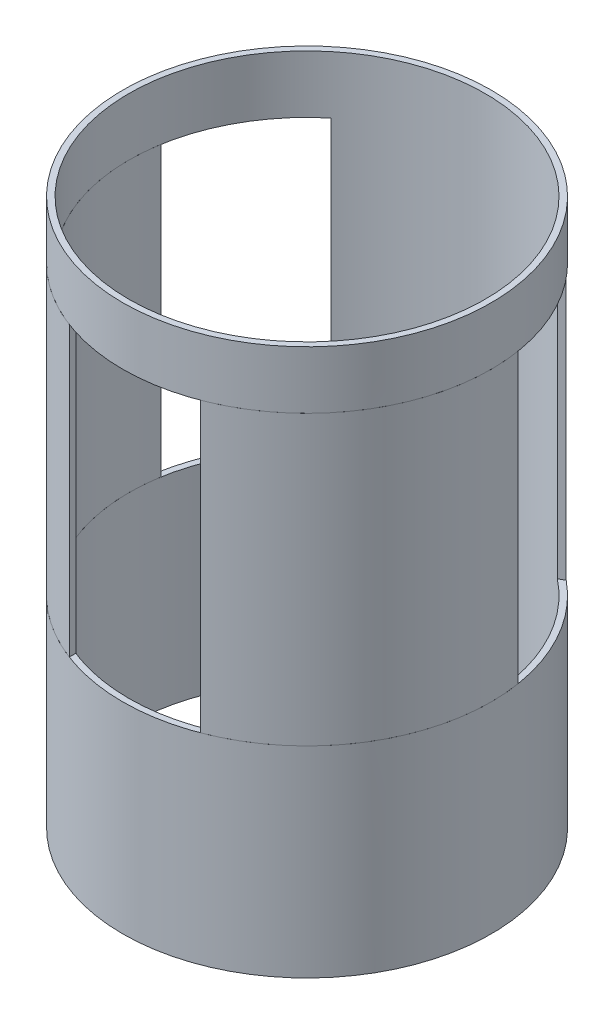
SolidWorks part; units mm, degrees
material "Carbon Fiber"
ref_plane "Front Plane" through (0, 0, 0) normal (0, 0, 1) x (1, 0, 0)
ref_plane "Top Plane" through (0, 0, 0) normal (0, 1, 0) x (1, 0, 0)
ref_plane "Right Plane" through (0, 0, 0) normal (1, 0, 0) x (0, 0, -1)
sketch "Sketch1" plane through (0, 0, 0) normal (0, 1, 0) x (1, 0, 0)
  line L0 (0, 0) -> (0, -68.75) construction
  line L1 (68.75, 0) -> (-68.75, 0) construction
  line L2 (-56.7965, 32.7915) -> (-44.5606, 53.9848)
  line L3 (0, 0) -> (59.5392, 34.375) construction
  line L4 (0, 0) -> (-59.5392, 34.375) construction
  line L5 (-44.5606, 53.9848) -> (-69.0325, 11.5982)
  line L6 (-54.2965, 37.1216) -> (-59.2965, 28.4614)
  line L7 (-59.2965, 28.4614) -> (-42.7188, 18.8902)
  line L8 (0, -65.583) -> (-24.4719, -65.583)
  line L9 (-24.4719, -65.583) -> (24.4719, -65.583)
  line L10 (-42.7188, 18.8902) -> (-37.7188, 27.5505)
  line L11 (-59.2965, 28.4614) -> (-61.8816, 29.9538)
  line L12 (-54.2965, 37.1216) -> (-37.7188, 27.5505)
  line L13 (-51.7965, 41.4517) -> (-55, 43.3013)
  line L14 (-61.7965, 24.1312) -> (-65, 25.9808)
  line L15 (-51.7965, 41.4517) -> (-30.8887, 29.3806) construction
  line L16 (-40.8887, 12.0601) -> (-30.8887, 29.3806) construction
  line L17 (-61.7965, 24.1312) -> (-40.8887, 12.0601) construction
  line L18 (56.7965, 32.7915) -> (69.0325, 11.5982)
  line L19 (69.0325, 11.5982) -> (44.5606, 53.9848)
  line L20 (59.2965, 28.4614) -> (54.2965, 37.1216)
  line L21 (54.2965, 37.1216) -> (37.7188, 27.5505)
  line L22 (37.7188, 27.5505) -> (42.7188, 18.8902)
  line L23 (54.2965, 37.1216) -> (56.8816, 38.6141)
  line L24 (59.2965, 28.4614) -> (42.7188, 18.8902)
  line L25 (61.7965, 24.1312) -> (65, 25.9808)
  line L26 (-5, -65.583) -> (5, -65.583)
  line L27 (5, -65.583) -> (5, -46.4407)
  line L28 (5, -46.4407) -> (-5, -46.4407)
  line L29 (5, -65.583) -> (5, -68.5679)
  line L30 (-5, -65.583) -> (-5, -46.4407)
  line L32 (51.7965, 41.4517) -> (55, 43.3013)
  line L33 (61.7965, 24.1312) -> (40.8887, 12.0601) construction
  line L34 (30.8887, 29.3806) -> (40.8887, 12.0601) construction
  line L35 (51.7965, 41.4517) -> (30.8887, 29.3806) construction
  line L36 (-24.4719, -65.583) -> (-24.4719, -64.2471)
  line L37 (24.4719, -65.583) -> (24.4719, -64.2471)
  line L38 (-69.0325, 11.5982) -> (-67.8756, 10.9302)
  line L39 (-10, -10) -> (10, -10)
  line L40 (-10, -10) -> (-10, 10)
  line L41 (-10, 10) -> (10, 10)
  line L42 (10, -10) -> (10, 10)
  line L43 (-10, -10) -> (10, 10) construction
  line L44 (-10, 10) -> (10, -10) construction
  line L45 (-44.5606, 53.9848) -> (-43.4036, 53.3168)
  line L46 (44.5606, 53.9848) -> (-67.8756, -10.9302)
  line L47 (69.0325, 11.5982) -> (67.8756, 10.9302)
  line L48 (-24.4719, -65.583) -> (-24.4719, -61.8334)
  line L49 (24.4719, -65.583) -> (24.4719, -61.8334)
  line L50 (69.0325, 11.5982) -> (65.7853, 9.7234)
  line L51 (-44.5606, 53.9848) -> (-42.3325, 51.2855)
  line L52 (-69.0325, 11.5982) -> (-65.5808, 11.0183)
  line L58 (-10, -65.583) -> (-10, -41.4407) construction
  line L59 (10, -41.4407) -> (-10, -41.4407) construction
  line L60 (10, -65.583) -> (10, -41.4407) construction
  line L61 (-10, -65.583) -> (-10, -69.282)
  line L62 (10, -65.583) -> (10, -69.282)
  line L63 (10, -65.583) -> (10, -68.5679) construction
  circle A0 centre (0, 0) radius 68.75
  circle A1 centre (0, 0) radius 70
  circle A2 centre (0, 0) radius 66.5
  point P14 (0, 0)
  point P26 (-40.2188, 23.2204)
  point P39 (0, -46.4407)
  point P51 (40.2188, 23.2204)
  point P58 (0, 0)
  point P67 (0, 0)
  point P68 (0, 0)
  point P71 (0, 0)
  point P81 (0, 0)
  dimension "D1" = 137.5
  dimension "D2" = 140
  dimension "D3" = 50
  dimension "D5" = 30
  dimension "D9" = 133
  dimension "D8" = 3
  dimension "D10" = 22.3093
  dimension "D4" = 30
  dimension "D7" = 5
  dimension "D6" = 5
extrude "Boss-Extrude7" add sketch "Sketch1" along normal blind 107.5 separate body contours A2 L52 A0 L46 | A2 L46 A0 L51 | A2 L49 A0 L50 | A2 L46 A0 L48 region at (-42.3631, 0, -52.7191) region at (-67.3493, 0, -0.4398) region at (-52.6561, 0, 41.7463) region at (67.6613, 0, -5.413)
extrude "Boss-Extrude8" add sketch "Sketch1<22>" along normal blind 21.5 from surface contours A2 L14 A0 L5 | A2 L5 A0 L52 | A2 L52 A0 L46 | A2 L46 A0 L48 | A2 L48 A0 L9 | A2 L9 A0 L61 | A2 L61 A0 L29 | A2 L29 A0 L62 | A2 L62 A0 L9 | A2 L9 A0 L49 | A2 L49 A0 L50 | A2 L50 A0 L19 | A2 L19 A0 L25 | A2 L19 A0 L46 | A2 L32 A0 L19 | A2 L23 A0 L32 | A2 L25 A0 L23 | A2 L46 A0 L51 | A2 L51 A0 L5 | A2 L5 A0 L13 | A2 L13 A0 L11 | A2 L11 A0 L14 region at (-61.9414, 0, -27.0976) region at (-57.1486, 0, -35.8935) region at (-50.672, 0, -45.1389) region at (-46.082, 0, -49.111) region at (-65.5724, 0, -15.3527) region at (-64.4275, 0, -21.3138) region at (-42.3631, 0, -52.7191) region at (-67.3493, 0, -0.4398) region at (45.7182, 0, -49.4428) region at (-52.6561, 0, 41.7463) region at (50.672, 0, -45.1389) region at (-19.9596, 0, 64.3145) region at (54.4379, 0, -40.094) region at (-13.7555, 0, 66.4527) region at (59.659, 0, -31.5454) region at (-2.5104, 0, 67.4389) region at (64.4275, 0, -21.3138) region at (7.5035, 0, 67.1916) region at (13.7555, 0, 66.4527) region at (65.6778, 0, -14.8717) region at (67.6613, 0, -5.413) region at (19.9596, 0, 64.3145) starting at face at (-52.1834, 107.5, 29.6722)
sketch "Sketch1<22>" plane through (0, 0, 0) normal (0, 1, 0) x (1, 0, 0) same geometry as "Sketch1"
extrude "Boss-Extrude9" add sketch "Sketch1<23>" against normal blind 75 contours A2 L46 A0 L51 | A2 L51 A0 L5 | A2 L13 A0 L11 | A2 L5 A0 L13 | A2 L11 A0 L14 | A2 L14 A0 L5 | A2 L5 A0 L52 | A2 L52 A0 L46 | A2 L46 A0 L48 | A2 L48 A0 L9 | A2 L9 A0 L61 | A2 L61 A0 L29 | A2 L29 A0 L62 | A2 L62 A0 L9 | A2 L9 A0 L49 | A2 L49 A0 L50 | A2 L50 A0 L19 | A2 L19 A0 L25 | A2 L25 A0 L23 | A2 L23 A0 L32 | A2 L32 A0 L19 | A2 L19 A0 L46 region at (-61.9414, 0, -27.0976) region at (-57.1486, 0, -35.8935) region at (-50.672, 0, -45.1389) region at (-46.082, 0, -49.111) region at (-65.5724, 0, -15.3527) region at (-64.4275, 0, -21.3138) region at (-42.3631, 0, -52.7191) region at (-67.3493, 0, -0.4398) region at (45.7182, 0, -49.4428) region at (-52.6561, 0, 41.7463) region at (50.672, 0, -45.1389) region at (-19.9596, 0, 64.3145) region at (54.4379, 0, -40.094) region at (-13.7555, 0, 66.4527) region at (59.659, 0, -31.5454) region at (-2.5104, 0, 67.4389) region at (64.4275, 0, -21.3138) region at (7.5035, 0, 67.1916) region at (13.7555, 0, 66.4527) region at (65.6778, 0, -14.8717) region at (67.6613, 0, -5.413) region at (19.9596, 0, 64.3145)
sketch "Sketch1<23>" plane through (0, 0, 0) normal (0, 1, 0) x (1, 0, 0) same geometry as "Sketch1"
